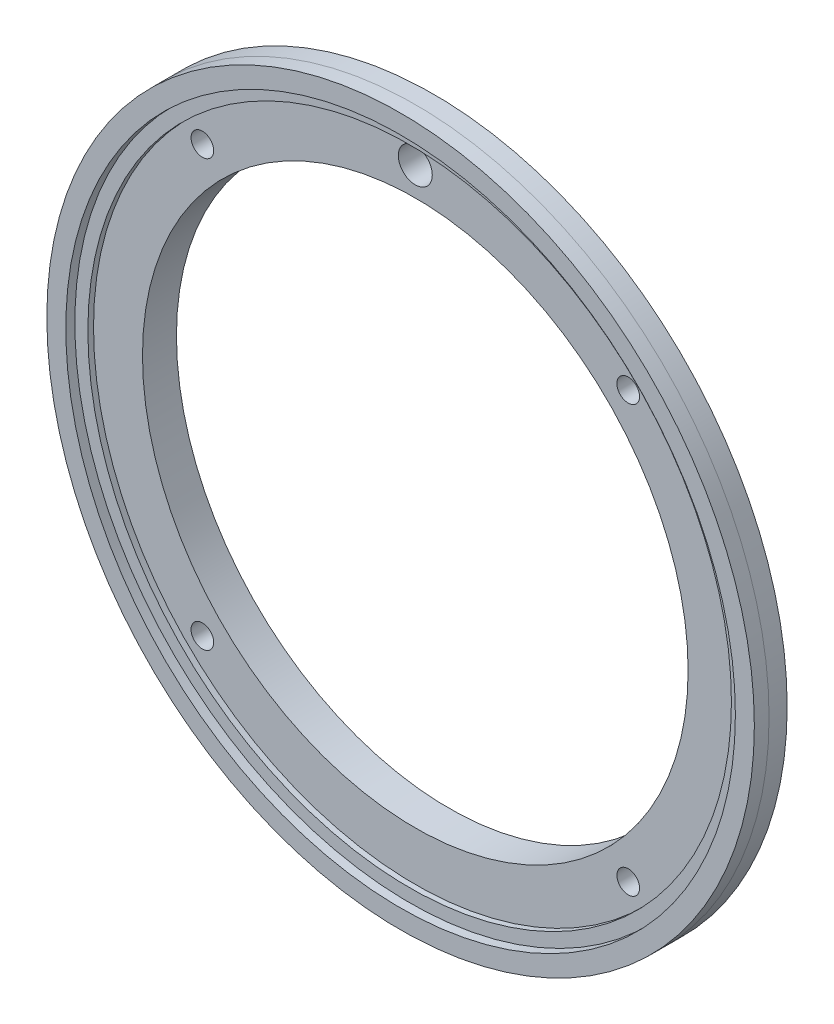
SolidWorks part; units mm, degrees
ref_plane "Front Plane" through (0, 0, 0) normal (0, 0, 1) x (1, 0, 0)
ref_plane "Top Plane" through (0, 0, 0) normal (0, 1, 0) x (1, 0, 0)
ref_plane "Right Plane" through (0, 0, 0) normal (1, 0, 0) x (0, 0, -1)
sketch "Sketch1" plane through (0, 0, 0) normal (0, 0, 1) x (1, 0, 0)
  circle A0 centre (0, 0) radius 28.3
  circle A1 centre (0, 0) radius 24.1
  dimension "D1" = 56.6
  dimension "D2" = 48.2
extrude "Boss-Extrude1" add sketch "Sketch1" along normal blind 0.6
sketch "Sketch2" plane through (0, 0, 0.6) normal (0, 0, 1) x (1, 0, 0)
  circle A0 centre (0, 0) radius 24.1 construction
  circle A1 centre (0, 0) radius 24.1
  circle A2 centre (0, 0) radius 29.4
  dimension "D1" = 58.8
extrude "Boss-Extrude2" add sketch "Sketch2" along normal offset from surface (0.8 mm away) 1.4 up to face at (28.3, 0, 0)
sketch "Sketch3" plane through (0, 0, 1.4) normal (0, 0, 1) x (1, 0, 0)
  circle A0 centre (0, 0) radius 24.1 construction
  circle A1 centre (0, 0) radius 24.1
  circle A2 centre (0, 0) radius 31.25
  dimension "D1" = 62.5
extrude "Boss-Extrude3" add sketch "Sketch3" along normal blind 1.6
sketch "Sketch4" plane through (0, 0, 3) normal (0, 0, 1) x (1, 0, 0)
  circle A0 centre (0, 0) radius 31.25 construction
  circle A1 centre (0, 0) radius 31.25
  circle A4 centre (0, 0) radius 28.425
  dimension "D1" = 56.85
extrude "Boss-Extrude4" add sketch "Sketch4" along normal blind 0.5
sketch "Sketch5" plane through (0, 0, 3.5) normal (0, 0, 1) x (1, 0, 0)
  circle A0 centre (0, 0) radius 31.25 construction
  circle A1 centre (0, 0) radius 31.25
  circle A2 centre (0, 0) radius 29.575
  dimension "D1" = 59.15
extrude "Boss-Extrude5" add sketch "Sketch5" along normal blind 0.8
sketch "Sketch6" plane through (0, 0, 0) normal (0, 0, -1) x (-1, 0, 0)
  line L0 (0, 0) -> (0, 31.25) construction
  line L1 (0, 0) -> (18.809, 18.809) construction
  circle A0 centre (0, 0) radius 31.25 construction
  circle A1 centre (0, 0) radius 26.6 construction
  circle A2 centre (18.809, 18.809) radius 1
  circle A3 centre (18.809, -18.809) radius 1
  circle A4 centre (0, 0) radius 26.6 construction
  circle A5 centre (-18.809, -18.809) radius 1
  circle A6 centre (0, 0) radius 26.6 construction
  circle A7 centre (-18.809, 18.809) radius 1
  circle A8 centre (0, 0) radius 26.6 construction
  circle A9 centre (0, 26.6) radius 1.5
  point P21 (0, 0)
  dimension "D1" = 53.2
  dimension "D3" = 2
  dimension "D5" = 3
  dimension "D2" = 45
  dimension "D4" = 4
extrude "Cut-Extrude1" cut sketch "Sketch6" against normal through all
sketch "Sketch7" plane through (0, 0, 0) normal (0, 0, -1) x (-1, 0, 0)
  line L0 (-1.5, 26.6) -> (-1.5, 28.2602)
  line L1 (1.5, 26.6) -> (1.5, 28.2602)
  circle A2 centre (0, 26.6) radius 1.5 construction
  circle A3 centre (0, 26.6) radius 1.5
  circle A4 centre (0, 0) radius 28.3 construction
  circle A5 centre (0, 0) radius 28.3
  circle M4 centre (0, 26.6) radius 1.5
  circle M6 centre (0, 0) radius 28.3
extrude "Cut-Extrude2" cut sketch "Sketch7" against normal up to surface (0.6 mm away) contours L1 L0 M4 M6 region at (1.4655, 27.4301, 0) up to face at (28.3, 0, 0.6)
split "Split1" bodies to split 107 resulting bodies 108 109 split by face at (19.809, 18.809, 3)
